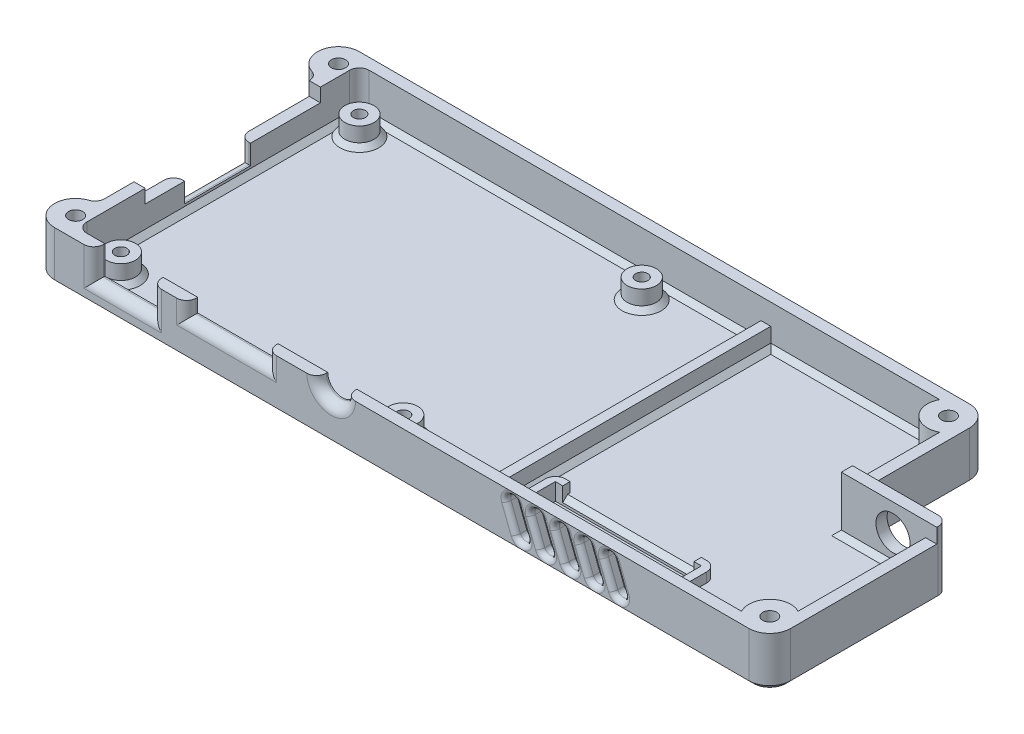
SolidWorks part; units mm, degrees
ref_plane "Front Plane" through (0, 0, 0) normal (0, 0, 1) x (1, 0, 0)
ref_plane "Top Plane" through (0, 0, 0) normal (0, 1, 0) x (1, 0, 0)
ref_plane "Right Plane" through (0, 0, 0) normal (1, 0, 0) x (0, 0, -1)
sketch "Sketch1" plane through (0, 0, 0) normal (0, 1, 0) x (1, 0, 0)
  line L0 (-71.5618, 3.106) -> (51.4382, 3.106) construction
  line L1 (-71.5618, 31.106) -> (51.4382, 31.106)
  line L2 (-71.5618, 31.106) -> (-71.5618, -24.894)
  line L3 (-71.5618, -24.894) -> (51.4382, -24.894)
  line L4 (51.4382, 31.106) -> (51.4382, -24.894)
  line L5 (-60.6618, -24.894) -> (-60.6618, -31.6828) construction
  line L6 (-68.0618, 27.606) -> (-10.0618, 27.606)
  line L7 (-68.0618, 27.606) -> (-68.0618, -21.394)
  line L8 (-68.0618, -21.394) -> (-10.0618, -21.394)
  line L9 (-10.0618, 27.606) -> (-10.0618, -21.394)
  line L10 (-39.5618, -24.894) -> (-39.5618, -31.6828) construction
  line L11 (-18.0618, -24.894) -> (-18.0618, -31.6828) construction
  line L12 (-65.4118, -26.5648) -> (-55.9118, -26.5648) construction
  line L13 (-48.0618, -26.5648) -> (-31.0618, -26.5648) construction
  line L14 (-22.0618, -26.5648) -> (-14.0618, -26.5648) construction
  line L15 (-72.5618, 9.606) -> (-72.5618, -3.394) construction
  line L16 (-71.5618, 3.106) -> (-72.5618, 3.106) construction
  dimension "D1" = 123
  dimension "D2" = 56
  dimension "D3" = 49
  dimension "D4" = 58
  dimension "D5" = 3.5
  dimension "D6" = 3.5
  dimension "D7" = 10.9
  dimension "D8" = 32
  dimension "D9" = 53.5
  dimension "D10" = 2
  dimension "D11" = 13
  dimension "D12" = 9.5
  dimension "D13" = 17
  dimension "D14" = 8
sketch "Sketch3" plane through (0, 0, 0) normal (0, 1, 0) x (1, 0, 0)
  line L0 (57.0382, -25.894) -> (69.7382, -25.894)
  line L1 (54.7382, 8.406) -> (72.0382, 8.406)
  line L2 (57.0382, 6.106) -> (69.7382, 6.106) construction
  line L3 (54.7382, -28.194) -> (72.0382, -28.194)
  line L4 (54.7382, 34.406) -> (-74.8618, 34.406)
  line L5 (-74.8618, 34.406) -> (-74.8618, -28.194)
  line L6 (-74.8618, -28.194) -> (54.7382, -28.194)
  line L7 (54.7382, 8.406) -> (54.7382, 34.406)
  line L8 (52.4382, 32.106) -> (-72.5618, 32.106)
  line L9 (52.4382, -25.894) -> (52.4382, 32.106)
  line L10 (-72.5618, -25.894) -> (52.4382, -25.894)
  line L11 (-72.5618, 32.106) -> (-72.5618, -25.894)
  line L12 (52.4382, 32.106) -> (-72.5618, 32.106)
  line L13 (52.4382, 6.106) -> (52.4382, 32.106)
  line L14 (-72.5618, -25.894) -> (52.4382, -25.894)
  line L15 (-72.5618, 32.106) -> (-72.5618, -25.894)
  line L16 (-10.0618, 3.106) -> (-10.0618, 34.406) construction
  line L17 (-71.5618, 3.106) -> (51.4382, 3.106) construction
  line L18 (72.0382, 8.406) -> (72.0382, -28.194)
  line L19 (69.7382, 6.106) -> (69.7382, -25.894)
  line L20 (-74.8618, 3.106) -> (52.7382, 3.106) construction
  line L21 (52.4382, 6.106) -> (69.7382, 6.106)
  line L22 (57.0382, -25.894) -> (52.4382, -25.894)
  line L23 (57.0382, 6.106) -> (57.0382, -25.894) construction
  line L24 (54.7382, 8.406) -> (54.7382, -28.194) construction
  line L25 (54.7382, -28.194) -> (54.7382, 34.406) construction
  line L26 (52.4382, -25.894) -> (52.4382, 32.106) construction
  dimension "D3" = 2.3
  dimension "D4" = 26
  dimension "D5" = 15
  dimension "D1" = 1
  dimension "D2" = 2.3
extrude "Boss-Extrude1" add sketch "Sketch3" along normal blind 10.3
sketch "Sketch5" plane through (0, 0, 0) normal (0, 1, 0) x (1, 0, 0)
  line L1 (-72.5618, 32.106) -> (52.4382, 32.106)
  line L2 (-72.5618, 32.106) -> (-72.5618, -25.894)
  line L3 (-72.5618, -25.894) -> (50.4382, -25.894)
  line L4 (52.4382, 32.106) -> (52.4382, 6.106)
  line L5 (52.4382, 6.106) -> (69.7382, 6.106)
  line L7 (50.4382, -25.894) -> (69.7382, -25.894)
  line L8 (69.7382, 6.106) -> (69.7382, -25.894)
extrude "Boss-Extrude2" add sketch "Sketch5" along normal blind 2
sketch "Sketch6" plane through (0, 2, 0) normal (0, 1, 0) x (1, 0, 0)
  circle A0 centre (-68.0618, 27.606) radius 3
  circle A1 centre (-68.0618, -21.394) radius 3
  circle A2 centre (-10.0618, -21.394) radius 3
  circle A3 centre (-10.0618, 27.606) radius 3
extrude "Boss-Extrude3" add sketch "Sketch6" along normal blind 4
hole_wizard "Ø2.5 (2.5) Diameter Hole1" positions "Sketch8" profile "Sketch9" hole size "Ø2.5" standard "ANSI Metric"
sketch "Sketch8" plane through (0, 6, 0) normal (0, 1, 0) x (1, 0, 0)
  point P0 (-68.0618, 27.606)
  point P3 (-10.0618, 27.606)
  point P6 (-10.0618, -21.394)
  point P9 (-68.0618, -21.394)
sketch "Sketch9" plane through (-68.0618, 6, -27.606) normal (1, 0, 0) x (0, 0, 1)
  line L0 (0, 0) -> (0, 8.7511)
  line L1 (0, 8.7511) -> (1.25, 8)
  line L2 (1.25, 8) -> (1.25, 0)
  line L5 (1.25, 0) -> (0, 0)
  line L10 (0, 8.7511) -> (-1.25, 8) construction
  line L11 (0, -6.35) -> (0, 107.95) construction
  dimension "Hole Dia." = 2.5
  dimension "Hole Depth" = 8
  dimension "Drill Angle" = 118
sketch "Sketch10" plane through (0, 2, 0) normal (0, 1, 0) x (1, 0, 0)
  line L0 (52.4382, 32.106) -> (-72.5618, 32.106) construction
  line L1 (9.9382, 32.106) -> (11.9382, 32.106)
  line L2 (9.9382, 32.106) -> (9.9382, -25.894)
  line L3 (9.9382, -25.894) -> (11.9382, -25.894)
  line L4 (11.9382, 32.106) -> (11.9382, -25.894)
  line L5 (-72.5618, -25.894) -> (69.7382, -25.894) construction
  line L6 (-10.0618, 27.606) -> (-10.0618, -21.394) construction
  dimension "D1" = 2
  dimension "D2" = 20
extrude "Boss-Extrude4" add sketch "Sketch10" along normal blind 4
sketch "Sketch11" plane through (0, 0, 28.194) normal (0, 0, 1) x (1, 0, 0)
  line L0 (-74.8618, 10.3) -> (-74.8618, 0) construction
  line L1 (-66.8618, 10.3) -> (-54.8618, 10.3)
  line L2 (-66.8618, 10.3) -> (-66.8618, 4.5)
  line L3 (-66.8618, 4.5) -> (-54.8618, 4.5)
  line L4 (-54.8618, 10.3) -> (-54.8618, 4.5)
  line L5 (-74.8618, 0) -> (72.0382, 0) construction
  line L6 (-60.8618, 10.3) -> (-60.6618, 0) construction
  line L7 (-65.4118, 0) -> (-55.9118, 0) construction
  line L9 (-47.778, 10.3) -> (-31.278, 10.3)
  line L10 (-47.778, 10.3) -> (-47.778, 7.5)
  line L11 (-47.778, 7.5) -> (-31.278, 7.5)
  line L12 (-31.278, 10.3) -> (-31.278, 7.5)
  line L13 (-68.0618, 0) -> (-10.0618, 0) construction
  line L14 (-39.5618, 0) -> (-39.528, 10.3) construction
  line L15 (-48.0618, 0) -> (-31.0618, 0) construction
  line L16 (-18.0618, 0) -> (-18.0618, 10.3) construction
  line L17 (-22.0618, 0) -> (-14.0618, 0) construction
  line L18 (-74.8618, 10.3) -> (72.0382, 10.3) construction
  circle A0 centre (-18.0618, 10.3) radius 3
  dimension "D5" = 6
  dimension "D1" = 4.5
  dimension "D2" = 12
  dimension "D3" = 7.5
  dimension "D4" = 16.5
  dimension "D6" = 8
extrude "Cut-Extrude1" cut sketch "Sketch11" against normal up to next
sketch "Sketch12" plane through (-74.8618, 0, 0) normal (-1, 0, 0) x (0, 0, 1)
  line L0 (-3.106, 0) -> (-3.106, 10.3) construction
  line L1 (-27.606, 0) -> (21.394, 0) construction
  line L2 (-34.406, 10.3) -> (28.194, 10.3) construction
  line L4 (-9.7329, 10.3) -> (3.7671, 10.3)
  line L5 (-9.7329, 10.3) -> (-9.7329, 3.5)
  line L6 (-9.7329, 3.5) -> (3.7671, 3.5)
  line L7 (3.7671, 10.3) -> (3.7671, 3.5)
  line L8 (-24.106, 10.3) -> (11.894, 10.3)
  line L9 (-24.106, 10.3) -> (-24.106, 7.5)
  line L10 (-24.106, 7.5) -> (11.894, 7.5)
  line L11 (11.894, 10.3) -> (11.894, 7.5)
  dimension "D1" = 13.5
  dimension "D2" = 3.5
  dimension "D3" = 7.5
  dimension "D4" = 36
extrude "Cut-Extrude2" cut sketch "Sketch12" against normal up to next contours L10 L11 L8 L9 | L7 L6 L5 L4
fillet "Fillet6" radius 2 1 edges at (52.4382, 6.15, -32.106)
fillet "Fillet8" radius 2 2 edges at (-72.5618, 6.15, 25.894) (-72.5618, 6.15, -32.106)
chamfer "Chamfer1" distance 1 angle 45 4 edges at (-68.0618, 2, 24.394) (-10.0618, 2, 24.394) (-10.0618, 2, -24.606) (-68.0618, 2, -24.606)
chamfer "Chamfer2" distance 1 angle 45 13 edges at (11.9382, 2, -3.106) (40.8382, 2, 25.894) (31.1882, 2, -32.106) (51.8524, 2, -31.5202) (52.4382, 2, -18.106) (-30.3118, 2, 25.894) (-71.976, 2, 25.3082) (-72.5618, 2, -3.106) (-71.976, 2, -31.5202) (9.9382, 2, -3.106) (-30.3118, 2, -32.106) (69.7382, 2, 9.894) (61.0882, 2, -6.106)
fillet "Fillet9" radius 2 9 edges at (-74.8618, 5.5, -9.7329) (-74.8618, 3.5, -2.9829) (-74.8618, 5.5, 3.7671) (-18.0618, 7.3, 28.194) (-31.278, 8.9, 28.194) (-47.778, 8.9, 28.194) (-39.528, 7.5, 28.194) (-54.8618, 7.4, 28.194) (-60.8618, 4.5, 28.194)
sketch "Sketch14" plane through (0, 10.3, 0) normal (0, 1, 0) x (1, 0, 0)
  line L1 (52.4382, 6.106) -> (72.0382, 6.106)
  line L2 (52.4382, 6.106) -> (52.4382, 8.406)
  line L3 (52.4382, 8.406) -> (72.0382, 8.406)
  line L4 (72.0382, 6.106) -> (72.0382, 8.406)
extrude "Boss-Extrude5" add sketch "Sketch14" along normal blind 3
sketch "Sketch13" plane through (0, 0, -8.406) normal (0, 0, -1) x (-1, 0, 0)
  line L0 (-72.0382, 13.3) -> (-72.0382, 0) construction
  circle A0 centre (-63.0382, 7.7621) radius 3.5
  circle A1 centre (-63.0382, 7.7621) radius 7.5 construction
  dimension "D1" = 9
extrude "Cut-Extrude3" cut sketch "Sketch13" against normal up to next
sketch "Sketch17" plane through (0, 0, 0) normal (0, 1, 0) x (1, 0, 0)
  line L0 (-74.8618, 34.406) -> (-74.8618, 24.106) construction
  line L1 (-74.8618, 34.406) -> (-74.8618, 25.806)
  line L2 (-74.8618, 25.806) -> (-74.659, 25.9406)
  line L3 (-74.8618, -19.594) -> (-74.8618, -28.194)
  line L4 (-74.8618, -28.194) -> (-74.659, -28.0594)
  arc A0 (-74.8618, -19.594) -> (-74.8618, -28.194) centre (-74.8618, -23.894) ccw
  arc A1 (-74.8618, 34.406) -> (-74.8618, 25.806) centre (-74.8618, 30.106) ccw
extrude "Boss-Extrude6" add sketch "Sketch17" along normal up to vertex (10.3 mm away) contours L1 A1 | L3 A0 region at (-76.6867, 0, -30.106) region at (-76.6867, 0, 23.894) up to point (-74.8618, 10.3, 28.194)
hole_wizard "Ø2.9 (2.9) Diameter Hole2" positions "Sketch19" profile "Sketch18" hole size "Ø2.9" standard "ANSI Metric" end condition up to next
sketch "Sketch19" plane through (0, 10.3, 0) normal (0, 1, 0) x (1, 0, 0)
  point P0 (-74.8618, 30.106)
sketch "Sketch18" plane through (-74.8618, 10.3, -30.106) normal (1, 0, 0) x (0, 0, 1)
  line L0 (0, 0) -> (0, 10.3)
  line L1 (0, 10.3) -> (1.45, 10.3)
  line L2 (1.45, 10.3) -> (1.45, 0)
  line L5 (1.45, 0) -> (0, 0)
  line L11 (0, -6.35) -> (0, 107.95) construction
  dimension "Thru Hole Dia." = 2.9
  dimension "Thru Hole Depth" = 10.3
hole_wizard "Ø2.9 (2.9) Diameter Hole1" positions "Sketch21" profile "Sketch20" hole size "Ø2.9" standard "ANSI Metric" end condition up to next
sketch "Sketch21" plane through (0, 10.3, 0) normal (0, 1, 0) x (1, 0, 0)
  point P0 (-74.8618, -23.894)
sketch "Sketch20" plane through (-74.8618, 10.3, 23.894) normal (1, 0, 0) x (0, 0, 1)
  line L0 (0, 0) -> (0, 10.3)
  line L1 (0, 10.3) -> (1.45, 10.3)
  line L2 (1.45, 10.3) -> (1.45, 0)
  line L5 (1.45, 0) -> (0, 0)
  line L11 (0, -6.35) -> (0, 107.95) construction
  dimension "Thru Hole Dia." = 2.9
  dimension "Thru Hole Depth" = 10.3
sketch "Sketch24" plane through (0, 2, 0) normal (0, 1, 0) x (1, 0, 0)
  line L0 (72.0382, -28.194) -> (72.0382, 8.406) construction
  line L1 (-74.8618, -28.194) -> (72.0382, -28.194) construction
  line L2 (54.7382, 8.406) -> (54.7382, 34.406) construction
  line L3 (54.7382, 34.406) -> (-74.8618, 34.406) construction
  circle A0 centre (67.7382, -23.894) radius 4.3
  circle A1 centre (50.4382, 30.106) radius 4.3
  dimension "D1" = 4.3
  dimension "D2" = 4.3
  dimension "D3" = 4.3
  dimension "D4" = 4.3
extrude "Boss-Extrude7" add sketch "Sketch24" along normal up to surface (8.3 mm away) up to face at (-74.8618, 10.3, 25.344)
hole_wizard "Ø2.9 (2.9) Diameter Hole3" positions "Sketch26" profile "Sketch25" hole size "Ø2.9" standard "ANSI Metric" end condition up to next
sketch "Sketch26" plane through (0, 10.3, 0) normal (0, 1, 0) x (1, 0, 0)
  point P0 (67.7382, -23.894)
sketch "Sketch25" plane through (67.7382, 10.3, 23.894) normal (1, 0, 0) x (0, 0, 1)
  line L0 (0, 0) -> (0, 10.3)
  line L1 (0, 10.3) -> (1.45, 10.3)
  line L2 (1.45, 10.3) -> (1.45, 0)
  line L5 (1.45, 0) -> (0, 0)
  line L11 (0, -6.35) -> (0, 107.95) construction
  dimension "Thru Hole Dia." = 2.9
  dimension "Thru Hole Depth" = 10.3
hole_wizard "Ø2.9 (2.9) Diameter Hole4" positions "Sketch28" profile "Sketch27" hole size "Ø2.9" standard "ANSI Metric" end condition up to next
sketch "Sketch28" plane through (0, 10.3, 0) normal (0, 1, 0) x (1, 0, 0)
  point P0 (50.4382, 30.106)
sketch "Sketch27" plane through (50.4382, 10.3, -30.106) normal (1, 0, 0) x (0, 0, 1)
  line L0 (0, 0) -> (0, 10.3)
  line L1 (0, 10.3) -> (1.45, 10.3)
  line L2 (1.45, 10.3) -> (1.45, 0)
  line L5 (1.45, 0) -> (0, 0)
  line L11 (0, -6.35) -> (0, 107.95) construction
  dimension "Thru Hole Dia." = 2.9
  dimension "Thru Hole Depth" = 10.3
fillet "Fillet10" radius 4.3 1 edges at (54.7382, 5.15, -34.406)
fillet "Fillet16" radius 4.3 1 edges at (72.0382, 5.15, 28.194)
fillet "Fillet17" radius 2 2 edges at (54.7382, 5.15, -8.406) (72.0382, 6.65, -8.406)
fillet "Fillet18" radius 2 2 edges at (-74.8618, 5.15, 19.594) (-74.8618, 5.15, -25.806)
fillet "Fillet19" radius 2 1 edges at (-66.8618, 6.4, 28.194)
sketch "Sketch29" plane through (0, 2, 0) normal (0, 1, 0) x (1, 0, 0)
  line L1 (15.4382, -15.644) -> (45.5382, -15.644)
  line L2 (15.4382, -15.644) -> (15.4382, -25.894)
  line L3 (15.4382, -25.894) -> (45.5382, -25.894)
  line L4 (45.5382, -15.644) -> (45.5382, -25.894)
  line L5 (-72.5618, -11.894) -> (-72.5618, -23.894) construction
  line L6 (-13.0618, -28.194) -> (67.7382, -28.194) construction
  dimension "D1" = 30.1
  dimension "D2" = 10.25
  dimension "D3" = 88
  dimension "D4" = 2.3
extrude "Cut-Extrude4" cut sketch "Sketch29" against normal blind 1.5 and the other way up to next
sketch "Sketch30" plane through (0, 2, 0) normal (0, 1, 0) x (1, 0, 0)
  line L4 (13.9382, -25.9084) -> (15.4382, -25.894)
  line L5 (15.4382, -25.894) -> (15.4382, -15.644)
  line L6 (15.4382, -15.644) -> (16.9593, -15.644)
  line L7 (45.4382, -15.644) -> (45.4382, -25.894)
  line L8 (13.9382, -14.144) -> (13.9382, -27.394)
  line L9 (13.9382, -27.394) -> (47.0382, -27.394)
  line L10 (47.0382, -27.394) -> (47.0382, -14.144)
  line L11 (47.0382, -14.144) -> (13.9382, -14.144)
  line L12 (13.9382, -14.144) -> (13.9382, -25.9084)
  line L13 (16.9593, -14.144) -> (16.9593, -15.644)
  line L14 (47.0382, -25.894) -> (47.0382, -14.144)
  line L15 (47.0382, -14.144) -> (43.9171, -14.144)
  line L16 (45.4382, -25.894) -> (47.0382, -25.894)
  line L17 (30.4382, -16.444) -> (30.4382, -22.6133) construction
  line L18 (43.9171, -14.144) -> (43.9171, -15.644)
  line L19 (16.9593, -14.144) -> (13.9382, -14.144)
  line L20 (43.9171, -15.644) -> (45.4382, -15.644)
  dimension "D1" = 1.5
extrude "Boss-Extrude8" add sketch "Sketch30" along normal blind 2
chamfer "Chamfer3" distance 1 angle 45 1 edges at (30.4382, 2, 15.644)
fillet "Fillet20" radius 2 2 edges at (13.9382, 3, 14.144) (47.0382, 3, 14.144)
sketch "Sketch31" plane through (0, 0, 28.194) normal (0, 0, 1) x (1, 0, 0)
  line L0 (19.0803, 8.1204) -> (20.9966, 3.179) construction
  line L2 (20.2457, 8.5724) -> (22.1621, 3.6309)
  line L3 (17.9149, 7.6684) -> (19.8312, 2.727)
  line L4 (24.0803, 8.1204) -> (25.9966, 3.179) construction
  line L5 (25.2457, 8.5724) -> (27.1621, 3.6309)
  line L6 (22.9149, 7.6684) -> (24.8312, 2.727)
  line L7 (29.0803, 8.1204) -> (30.9966, 3.179) construction
  line L8 (30.2457, 8.5724) -> (32.1621, 3.6309)
  line L9 (27.9149, 7.6684) -> (29.8312, 2.727)
  line L10 (34.0803, 8.1204) -> (35.9966, 3.179) construction
  line L11 (35.2457, 8.5724) -> (37.1621, 3.6309)
  line L12 (32.9149, 7.6684) -> (34.8312, 2.727)
  line L13 (39.0803, 8.1204) -> (40.9966, 3.179) construction
  line L14 (40.2457, 8.5724) -> (42.1621, 3.6309)
  line L15 (37.9149, 7.6684) -> (39.8312, 2.727)
  arc A0 (20.2457, 8.5724) -> (17.9149, 7.6684) centre (19.0803, 8.1204) ccw
  arc A1 (19.8312, 2.727) -> (22.1621, 3.6309) centre (20.9966, 3.179) ccw
  arc A2 (25.2457, 8.5724) -> (22.9149, 7.6684) centre (24.0803, 8.1204) ccw
  arc A3 (24.8312, 2.727) -> (27.1621, 3.6309) centre (25.9966, 3.179) ccw
  arc A4 (30.2457, 8.5724) -> (27.9149, 7.6684) centre (29.0803, 8.1204) ccw
  arc A5 (29.8312, 2.727) -> (32.1621, 3.6309) centre (30.9966, 3.179) ccw
  arc A6 (35.2457, 8.5724) -> (32.9149, 7.6684) centre (34.0803, 8.1204) ccw
  arc A7 (34.8312, 2.727) -> (37.1621, 3.6309) centre (35.9966, 3.179) ccw
  arc A8 (40.2457, 8.5724) -> (37.9149, 7.6684) centre (39.0803, 8.1204) ccw
  arc A9 (39.8312, 2.727) -> (42.1621, 3.6309) centre (40.9966, 3.179) ccw
  point P4 (20.0385, 5.6497)
  point P13 (25.0385, 5.6497)
  point P20 (30.0385, 5.6497)
  point P27 (35.0385, 5.6497)
  point P34 (40.0385, 5.6497)
  dimension "D1" = 5
extrude "Cut-Extrude5" cut sketch "Sketch31" against normal up to next
chamfer "Chamfer5" distance 1 angle 45 14 edges at (-79.1058, 0, 24.5855) (-3.5618, 0, 28.194) (-75.2385, 0, 19.0883) (70.7788, 0, 26.9346) (-74.8618, 0, -3.106) (72.0382, 0, 8.744) (-75.2385, 0, -25.3002) (71.4524, 0, -7.8202) (-79.1058, 0, -30.7975) (63.3882, 0, -8.406) (-12.2118, 0, -34.406) (55.324, 0, -8.9918) (53.4788, 0, -33.1466) (54.7382, 0, -20.256)
fillet "Fillet21" radius 1 20 edges at (38.6284, 9.2858, 28.194) (41.2039, 6.1016, 28.194) (41.4486, 2.0135, 28.194) (33.6284, 9.2858, 28.194) (36.2039, 6.1016, 28.194) (36.4486, 2.0135, 28.194) (28.6284, 9.2858, 28.194) (31.2039, 6.1016, 28.194) (31.4486, 2.0135, 28.194) (23.6284, 9.2858, 28.194) (26.2039, 6.1016, 28.194) (26.4486, 2.0135, 28.194) (18.6284, 9.2858, 28.194) (21.2039, 6.1016, 28.194) (21.4486, 2.0135, 28.194) (38.873, 5.1977, 28.194) (33.873, 5.1977, 28.194) (28.873, 5.1977, 28.194) (23.873, 5.1977, 28.194) (18.873, 5.1977, 28.194)
